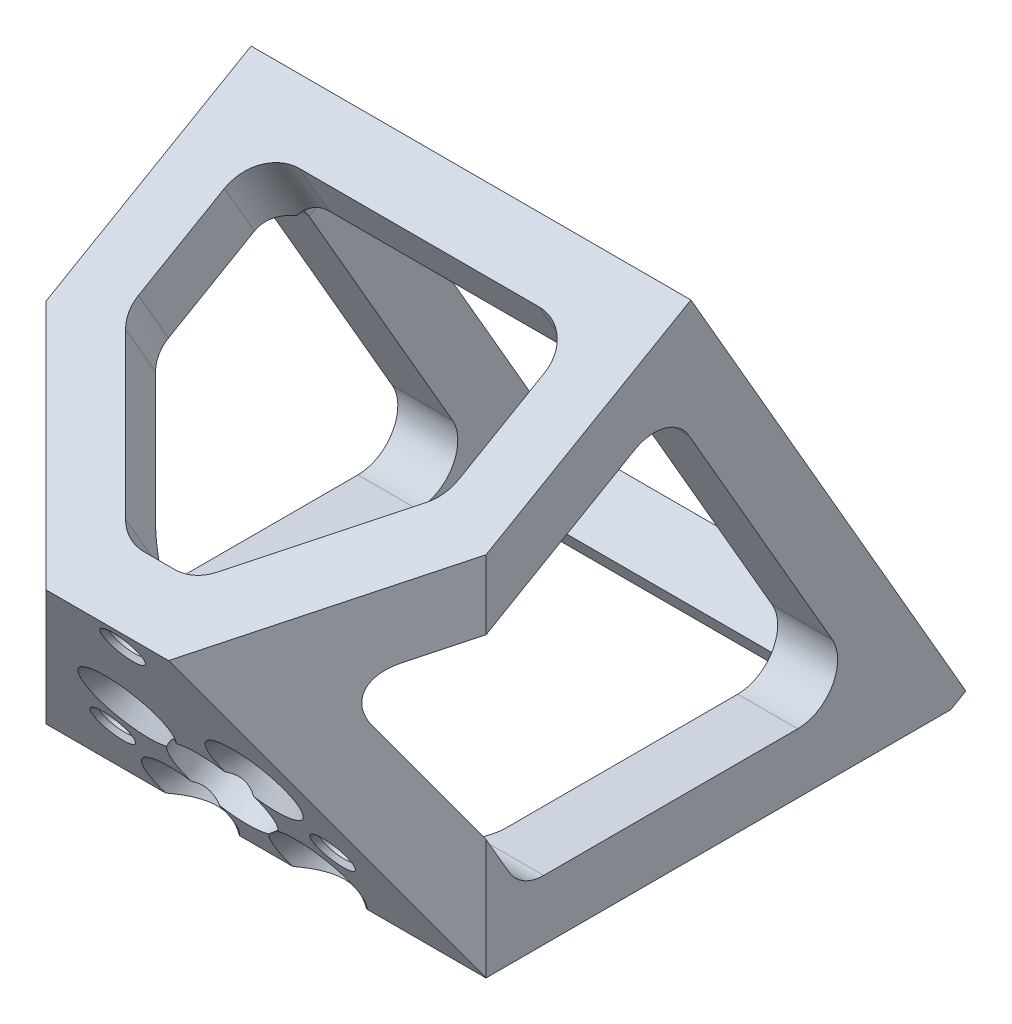
SolidWorks part; units mm, degrees
ref_plane "Front Plane" through (0, 0, 0) normal (0, 0, 1) x (1, 0, 0)
ref_plane "Top Plane" through (0, 0, 0) normal (0, 1, 0) x (1, 0, 0)
ref_plane "Right Plane" through (0, 0, 0) normal (1, 0, 0) x (0, 0, -1)
sketch "Sketch1" plane through (0, 0, 0) normal (1, 0, 0) x (0, 0, -1)
  line L0 (0, 0) -> (24.2487, 0)
  line L1 (24.2487, 0) -> (10.2487, 24.2487)
  line L2 (10.2487, 24.2487) -> (-7.9378, 13.7487)
  line L3 (-7.9378, 13.7487) -> (0, 0)
  point P3 (9.8957, 21.6506)
  point P6 (6.0713, 21.6506)
  dimension "D1" = 28
  dimension "D2" = 24.2487
  dimension "D3" = 60
  dimension "D4" = 21
extrude "Boss-Extrude1" add sketch "Sketch1" along normal blind 22
sketch "Sketch2" plane through (22, 0, 0) normal (1, 0, 0) x (0, 0, -1)
  line L0 (-3.8397, 12.6506) -> (1.7321, 3)
  line L1 (1.7321, 3) -> (19.0526, 3)
  line L2 (19.0526, 3) -> (9.1506, 20.1506)
  line L3 (9.1506, 20.1506) -> (-3.8397, 12.6506)
  line L4 (-7.9378, 13.7487) -> (0, 0)
  line L5 (0, 0) -> (24.2487, 0)
  line L6 (24.2487, 0) -> (10.2487, 24.2487)
  line L7 (10.2487, 24.2487) -> (-7.9378, 13.7487)
  line L8 (-7.9378, 13.7487) -> (0, 0) construction
  line L9 (0, 0) -> (24.2487, 0) construction
  line L10 (24.2487, 0) -> (10.2487, 24.2487) construction
  line L11 (10.2487, 24.2487) -> (-7.9378, 13.7487) construction
  dimension "D2" = 3
extrude "Cut-Extrude1" cut sketch "Sketch2" against normal through all both and the other way through all
sketch "Sketch12" plane through (0, 0, 0) normal (0, -1, 0) x (1, 0, 0)
  line L0 (22, 0) -> (11, 11)
  line L1 (11, 11) -> (0, 0)
  line L3 (22, 0) -> (22, 20.987)
  line L4 (22, 20.987) -> (0, 20.987)
  line L5 (0, 20.987) -> (0, 0)
  point P9 (22, -0.4352)
extrude "Cut-Extrude5" cut sketch "Sketch12" against normal through all both and the other way through all
sketch "Sketch3" plane through (0, 10.5, -18.1865) normal (0, 0.5, -0.866) x (-1, 0, 0)
  line L0 (-19, 12.8756) -> (-19, -9.1244)
  line L1 (-19, -9.1244) -> (-3, -9.1244)
  line L2 (-3, -9.1244) -> (-3, 12.8756)
  line L3 (-3, 12.8756) -> (-19, 12.8756)
  line L4 (0, -12.1244) -> (0, 15.8756)
  line L5 (0, 15.8756) -> (-22, 15.8756)
  line L6 (-22, 15.8756) -> (-22, -12.1244)
  line L7 (-22, -12.1244) -> (0, -12.1244)
  line L8 (0, -12.1244) -> (0, 15.8756) construction
  line L9 (0, 15.8756) -> (-22, 15.8756) construction
  line L10 (-22, 15.8756) -> (-22, -12.1244) construction
  line L11 (-22, -12.1244) -> (0, -12.1244) construction
  dimension "D2" = 3
extrude "Cut-Extrude2" cut sketch "Sketch3" against normal up to surface (18 mm away) up to face at (11, 7.2169, 0.7026)
fillet "Fillet1" radius 2 7 edges at (1.5, 20.1506, -9.1506) (20.5, 20.1506, -9.1506) (1.5, 3, -19.0526) (20.5, 3, -19.0526) (20.5, 3, -1.7321) (1.5, 3, -1.7321) (11, 12.6506, 3.8397)
sketch "Sketch4" plane through (0, 13.7487, 7.9378) normal (0, 0.866, 0.5) x (1, 0, 0)
  line L8 (3, 18) -> (3, 10.2843)
  line L9 (9.3084, 3) -> (12.6916, 3)
  line L10 (19, 10.2843) -> (19, 18)
  line L11 (19, 18) -> (3, 18)
  line L12 (3, 18) -> (3, 10.2843)
  line L13 (9.3084, 3) -> (12.6916, 3)
  line L14 (19, 10.2843) -> (19, 18)
  line L15 (19, 18) -> (3, 18)
  line L18 (12.6916, 3) -> (19, 10.2843)
  line L19 (12.6916, 3) -> (19, 10.2843)
  line L20 (3, 10.2843) -> (9.3084, 3)
  line L21 (3, 10.2843) -> (9.3084, 3)
  dimension "D1" = 3
extrude "Cut-Extrude3" cut sketch "Sketch4" against normal through all
fillet "Fillet5" radius 2 8 edges at (19, 2, -2.3094) (3, 2, -2.3094) (19, 21.4497, -8.4006) (3, 21.4497, -8.4006) (19, 17.5918, -1.7186) (3, 17.5918, -1.7186) (9.3084, 13.0836, 4.0897) (12.6916, 13.0836, 4.0897)
fillet "Fillet6" radius 2 4 edges at (19, 1.8481, -21.4497) (3, 1.8481, -21.4497) (3, 20.4006, -9.5836) (19, 20.4006, -9.5836)
fillet "Fillet7" radius 2 2 edges at (3, 1.4151, -19.9676) (19, 1.4151, -19.9676)
chamfer "Chamfer1" distance 1 angle 30 1 edges at (11, 0, -24.2487) first distance on face at (11, 0, -12.1244)
hole_wizard "M2x0.4 Tapped Hole1" positions "Sketch6" profile "Sketch7" tap size "M2x0.4" standard "ANSI Metric"
sketch "Sketch6" plane through (0, 10.5, -18.1865) normal (0, 0.5, -0.866) x (-1, 0, 0)
  line L1 (-19, 12.8756) -> (-22, 12.8756) construction
  line L2 (-19, 15.8756) -> (-19, 12.8756) construction
  line L3 (-19, 15.8756) -> (-19, 12.8756) construction
  line L4 (-22, -11.6244) -> (0, -11.6244) construction
  line L5 (-11, 15.8756) -> (-11, -11.6244) construction
  line L6 (-22, 15.8756) -> (0, 15.8756) construction
  line L7 (-19, 12.8756) -> (-22, 12.8756) construction
  line L8 (-22, -11.6244) -> (-22, 15.8756) construction
  point P0 (-20.5, 14.3756)
  point P7 (-20.5, -6.6244)
  point P12 (-20.5, 12.8756)
  point P13 (-19, 14.3756)
  point P24 (-1.5, -6.6244)
  point P25 (-1.5, 14.3756)
  point P28 (-20.4116, 12.8756)
  dimension "D1" = 5
cosmetic thread "Hole Thread1" parameters "D1"=2.4, "D2"=2
cosmetic thread "Hole Thread2" parameters "D1"=2.4, "D2"=2
cosmetic thread "Hole Thread3" parameters "D1"=2.4, "D2"=2
cosmetic thread "Hole Thread4" parameters "D1"=2.4, "D2"=2
sketch "Sketch7" plane through (20.5, 22.9497, -10.9987) normal (1, 0, 0) x (0, 0.866, 0.5)
  line L0 (0, 0) -> (0, 4.0807)
  line L1 (0, 4.0807) -> (0.8, 3.6)
  line L2 (0.8, 3.6) -> (0.8, 0)
  line L5 (0.8, 0) -> (0, 0)
  line L10 (0, 4.0807) -> (-0.8, 3.6) construction
  line L11 (0, -6.35) -> (0, 107.95) construction
  dimension "Tap Drill Dia." = 1.6
  dimension "Tap Drill Depth" = 3.6
  dimension "Drill Angle" = 118
hole_wizard "Ø5.0mm Dowel Hole1" positions "Sketch8" profile "Sketch9" hole size "Ø5.0" standard "ANSI Metric"
sketch "Sketch8" plane through (0, 0, 0) normal (0, -0.5, 0.866) x (1, 0, 0)
  line L0 (17, 10.8756) -> (5, -7.1244) construction
  arc A0 (19, 10.8756) -> (17, 12.8756) centre (17, 10.8756) ccw construction
  arc A1 (3, -7.1244) -> (5, -9.1244) centre (5, -7.1244) ccw construction
  point P0 (11, 4.3756)
  point P7 (0, 0)
  point P8 (0, 0)
  point P10 (0, 0)
  point P11 (0, 0)
  point P12 (0, 0)
  point P15 (0, 0)
  point P19 (0, 0)
  point P23 (0, 0)
  point P24 (9.2247, 7.9387)
  point P25 (11, 1.8756)
  dimension "D1" = 2.5
sketch "Sketch9" plane through (11, 3.7894, 2.1878) normal (1, 0, 0) x (0, -0.866, -0.5)
  line L0 (0, 0) -> (0, 19.5012)
  line L1 (0, 19.5012) -> (2.5, 17.999)
  line L2 (2.5, 17.999) -> (2.5, 0)
  line L5 (2.5, 0) -> (0, 0)
  line L10 (0, 19.5012) -> (-2.5, 17.999) construction
  line L11 (0, -6.35) -> (0, 107.95) construction
  dimension "Hole Dia." = 5
  dimension "Hole Depth" = 17.999
  dimension "Drill Angle" = 118
hole_wizard "CSK for M2 Flat Head Machine Screw1" positions "Sketch10" profile "Sketch11" countersink size "M2" standard "ANSI Metric"
sketch "Sketch10" plane through (0, 0, 0) normal (0, -0.5, 0.866) x (1, 0, 0)
  line L1 (7.818, 7.5576) -> (14.182, 7.5576)
  line L2 (7.818, 7.5576) -> (7.818, 1.1937)
  line L3 (7.818, 1.1937) -> (14.182, 1.1937)
  line L4 (14.182, 7.5576) -> (14.182, 1.1937)
  line L5 (7.818, 7.5576) -> (14.182, 1.1937) construction
  circle A0 centre (11, 4.3756) radius 2.5 construction
  point P0 (7.818, 7.5576)
  point P2 (14.182, 7.5576)
  point P4 (14.182, 1.1937)
  point P6 (7.818, 1.1937)
  point P112 (11, 4.3756)
  dimension "D1" = 9
sketch "Sketch11" plane through (7.818, 6.5451, 3.7788) normal (1, 0, 0) x (0, -0.866, -0.5)
  line L0 (0, 0) -> (0, 5.721)
  line L1 (0, 5.721) -> (1.2, 5)
  line L2 (1.2, 5) -> (1.2, 1)
  line L3 (1.2, 1) -> (2.2, 0)
  line L5 (2.2, 0) -> (0, 0)
  line L6 (-1.2, 1) -> (-2.2, 0) construction
  line L10 (0, 5.721) -> (-1.2, 5) construction
  line L11 (0, -6.35) -> (0, 107.95) construction
  dimension "Hole Dia." = 2.4
  dimension "Hole Depth" = 5
  dimension "Near C'Sink Dia." = 4.4
  dimension "Near C'Sink Angle" = 90
  dimension "Drill Angle" = 118
hole_wizard "M2x0.4 Tapped Hole2" positions "Sketch13" profile "Sketch14" tap size "M2x0.4" standard "ANSI Metric"
sketch "Sketch13" plane through (0, 0, 0) normal (0, -0.5, 0.866) x (1, 0, 0)
  line L0 (5.5, 4.35) -> (16.5, 4.35) construction
  line L2 (11, 14.35) -> (11, 4.35) construction
  line L4 (14.0622, 15.8756) -> (7.9378, 15.8756) construction
  line L5 (5.97, 0) -> (0, 0) construction
  point P0 (11, 14.35)
  point P3 (5.5, 4.35)
  point P6 (16.5, 4.35)
  point P20 (11, 15.8756)
  point P23 (0, 0)
  point P24 (0, 0)
  point P25 (0, 0)
  dimension "D1" = 4.35
  dimension "D2" = 11
  dimension "D3" = 10
sketch "Sketch14" plane through (11, 12.4275, 7.175) normal (1, 0, 0) x (0, -0.866, -0.5)
  line L0 (0, 0) -> (0, 5.6807)
  line L1 (0, 5.6807) -> (0.8, 5.2)
  line L2 (0.8, 5.2) -> (0.8, 0.225)
  line L3 (0.8, 0.225) -> (1.025, 0)
  line L5 (1.025, 0) -> (0, 0)
  line L6 (-0.8, 0.225) -> (-1.025, 0) construction
  line L10 (0, 5.6807) -> (-0.8, 5.2) construction
  line L11 (0, -6.35) -> (0, 107.95) construction
  dimension "Tap Drill Dia." = 1.6
  dimension "Tap Drill Depth" = 5.2
  dimension "Near C'Sink Dia." = 2.05
  dimension "Near C'Sink Angle" = 90
  dimension "Drill Angle" = 118
cosmetic thread "Hole Thread5" parameters "D1"=3, "D2"=2
cosmetic thread "Hole Thread6" parameters "D1"=3, "D2"=2
cosmetic thread "Hole Thread7" parameters "D1"=3.0001, "D2"=2
equation "\"strutWidth\"= 3mm"
equation "\"D2@Sketch2\"=\"strutWidth\""
equation "\"D2@Sketch3\"=\"strutWidth\""
equation "\"D1@Sketch4\"=\"strutWidth\""
equation "\"cutterRadius\"= 2mm"
equation "\"D1@Fillet1\"=\"cutterRadius\""
equation "\"D1@Fillet5\"=\"cutterRadius\""
equation "\"D1@Fillet6\"=\"cutterRadius\""
equation "\"D1@Fillet7\"=\"cutterRadius\""
